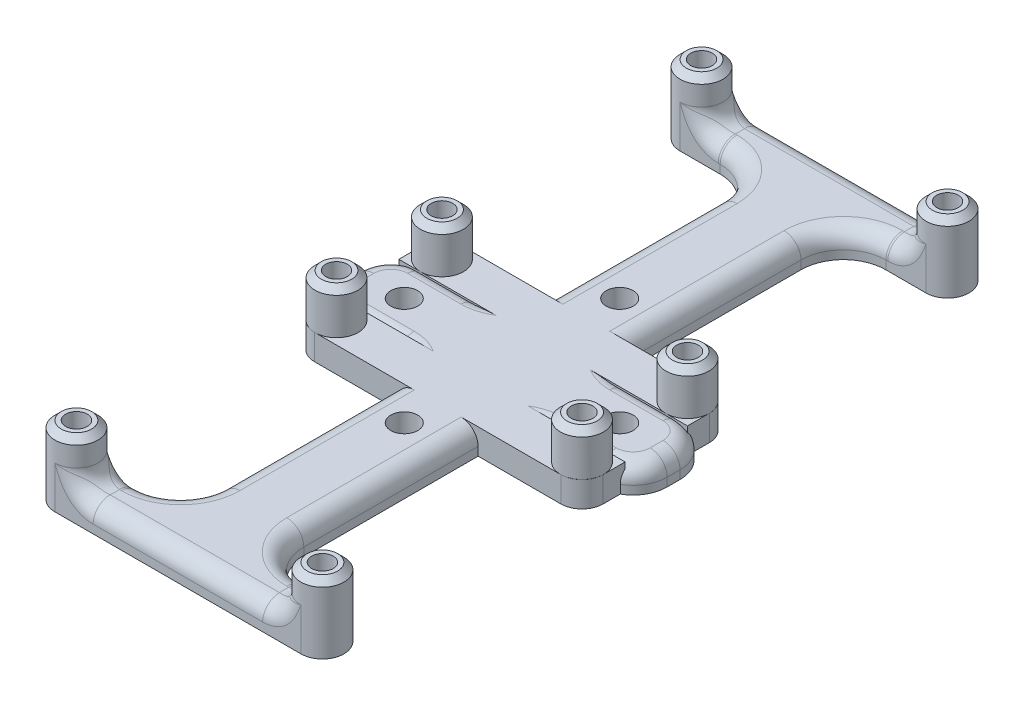
SolidWorks part; units mm, degrees
ref_plane "Front Plane" through (0, 0, 0) normal (0, 0, 1) x (1, 0, 0)
ref_plane "Top Plane" through (0, 0, 0) normal (0, 1, 0) x (1, 0, 0)
ref_plane "Right Plane" through (0, 0, 0) normal (1, 0, 0) x (0, 0, -1)
sketch "Sketch1" plane through (0, 0, 0) normal (0, 1, 0) x (1, 0, 0)
  line L1 (-4.7625, -34.305) -> (4.7625, -34.305)
  line L2 (-4.7625, -34.305) -> (-4.7625, 34.305)
  line L3 (-4.7625, 34.305) -> (4.7625, 34.305)
  line L4 (4.7625, -34.305) -> (4.7625, 34.305)
  line L5 (-4.7625, -34.305) -> (4.7625, 34.305) construction
  line L6 (-4.7625, 34.305) -> (4.7625, -34.305) construction
  line L7 (-14.5, 39.385) -> (14.5, 39.385)
  line L9 (-14.5, 34.305) -> (14.5, 34.305)
  line L11 (-14.5, 39.385) -> (14.5, 34.305) construction
  line L12 (-14.5, 34.305) -> (14.5, 39.385) construction
  line L13 (-14.5, -39.385) -> (14.5, -39.385)
  line L15 (-14.5, -34.305) -> (14.5, -34.305)
  line L17 (-14.5, -39.385) -> (14.5, -34.305) construction
  line L18 (-14.5, -34.305) -> (14.5, -39.385) construction
  arc A2 (-14.5, 34.305) -> (-14.5, 39.385) centre (-14.5, 36.845) cw
  arc A3 (14.5, 34.305) -> (14.5, 39.385) centre (14.5, 36.845) ccw
  arc A4 (-14.5, -39.385) -> (-14.5, -34.305) centre (-14.5, -36.845) cw
  arc A5 (14.5, -39.385) -> (14.5, -34.305) centre (14.5, -36.845) ccw
  point P0 (0, 0)
  point P6 (0, 36.845)
  point P11 (0, -36.845)
  dimension "D4" = 29
  dimension "D1" = 9.525
  dimension "D2" = 5.08
  dimension "D3" = 5.08
  dimension "D5" = 73.69
extrude "Boss-Extrude1" add sketch "Sketch1" along normal blind 3 contours L13 A5 L15 L1 A4 | L1 L4 L3 L2 | L9 A3 L7 A2 L3 region at (0, 0, 0) region at (0, 0, 36.845) region at (0, 0, -36.845)
sketch "Sketch2" plane through (0, 3, 0) normal (0, 1, 0) x (1, 0, 0)
  line L0 (0, 12.7) -> (0, -12.7) construction
  circle A0 centre (0, 12.7) radius 1.5875
  circle A1 centre (0, -12.7) radius 1.5875
  dimension "D2" = 3.175
  dimension "D3" = 3.175
  dimension "D1" = 25.4
extrude "Cut-Extrude1" cut sketch "Sketch2" against normal through all
sketch "Sketch3" plane through (0, 3, 0) normal (0, 1, 0) x (1, 0, 0)
  circle A0 centre (-14.5, 36.845) radius 2.54
  circle A1 centre (14.5, 36.845) radius 2.54
  circle A2 centre (14.5, -36.845) radius 2.54
  circle A3 centre (-14.5, -36.845) radius 2.54
  arc A4 (-14.5, 39.385) -> (-14.5, 34.305) centre (-14.5, 36.845) ccw construction
  arc A5 (14.5, 34.305) -> (14.5, 39.385) centre (14.5, 36.845) ccw construction
  arc A6 (-14.5, -34.305) -> (-14.5, -39.385) centre (-14.5, -36.845) ccw construction
  arc A7 (14.5, -39.385) -> (14.5, -34.305) centre (14.5, -36.845) ccw construction
extrude "Boss-Extrude2" add sketch "Sketch3" along normal blind 5.08
sketch "Sketch4" plane through (0, 8.08, 0) normal (0, 1, 0) x (1, 0, 0)
  circle A0 centre (-14.5, 36.845) radius 1.27
  circle A1 centre (14.5, 36.845) radius 1.27
  circle A2 centre (14.5, -36.845) radius 1.27
  circle A3 centre (-14.5, -36.845) radius 1.27
  dimension "D1" = 2.54
  dimension "D2" = 2.54
  dimension "D3" = 2.54
  dimension "D4" = 2.54
extrude "Cut-Extrude2" cut sketch "Sketch4" against normal blind 3.2004
sketch "Sketch5" plane through (0, 4.8796, 0) normal (0, 1, 0) x (1, 0, 0)
  circle A0 centre (-14.5, 36.845) radius 0.875
  circle A1 centre (14.5, 36.845) radius 0.875
  circle A2 centre (14.5, -36.845) radius 0.875
  circle A3 centre (-14.5, -36.845) radius 0.875
  dimension "D1" = 1.75
  dimension "D2" = 1.75
  dimension "D3" = 1.75
  dimension "D4" = 1.75
extrude "Cut-Extrude3" cut sketch "Sketch5" against normal through all
chamfer "Chamfer1" distance 0.75 angle 45 4 edges at (-14.5, 8.08, -34.305) (14.5, 8.08, -34.305) (14.5, 8.08, 39.385) (-14.5, 8.08, 39.385)
fillet "Fillet1" radius 5 4 edges at (-4.7625, 1.5, -34.305) (4.7625, 1.5, -34.305) (-4.7625, 1.5, 34.305) (4.7625, 1.5, 34.305)
fillet "Fillet2" radius 2 4 edges at (-11.96, 3, 36.845) (11.96, 3, 36.845) (11.96, 3, -36.845) (-11.96, 3, -36.845)
sketch "Sketch6" plane through (0, 3, 0) normal (0, 1, 0) x (1, 0, 0)
  line L1 (-19.05, -4.7625) -> (19.05, -4.7625)
  line L2 (-19.05, -4.7625) -> (-19.05, 4.7625)
  line L3 (-19.05, 4.7625) -> (19.05, 4.7625)
  line L4 (19.05, -4.7625) -> (19.05, 4.7625)
  line L5 (-19.05, -4.7625) -> (19.05, 4.7625) construction
  line L6 (-19.05, 4.7625) -> (19.05, -4.7625) construction
  point P0 (0, 0)
  dimension "D1" = 9.525
  dimension "D2" = 38.1
extrude "Boss-Extrude3" add sketch "Sketch6" against normal up to surface (3 mm away) up to face at (-14.5, 0, 37.72)
fillet "Fillet3" radius 4 8 edges at (-4.7625, 1.5, -4.7625) (-19.05, 1.5, -4.7625) (-19.05, 1.5, 4.7625) (-4.7625, 1.5, 4.7625) (4.7625, 1.5, 4.7625) (4.7625, 1.5, -4.7625) (19.05, 1.5, 4.7625) (19.05, 1.5, -4.7625)
sketch "Sketch7" plane through (0, 3, 0) normal (0, 1, 0) x (1, 0, 0)
  line L0 (-12.7, 0) -> (12.7, 0) construction
  circle A0 centre (-12.7, 0) radius 1.5875
  circle A1 centre (12.7, 0) radius 1.5875
  dimension "D2" = 3.175
  dimension "D3" = 3.175
  dimension "D1" = 25.4
extrude "Cut-Extrude4" cut sketch "Sketch7" against normal through all
fillet "Fillet4" radius 2 30 edges at (11.737, 3.1613, 34.305) (10.2498, 3, 34.305) (6.227, 3, 32.8405) (4.7625, 3, 19.0337) (11.737, 3.1613, -34.305) (10.2498, 3, -34.305) (6.227, 3, -32.8405) (4.7625, 3, -19.0337) (5.9341, 3, -5.9341) (11.9062, 3, -4.7625) (17.8784, 3, -3.5909) (19.05, 3, 0) (17.8784, 3, 3.5909) (11.9062, 3, 4.7625) (-11.737, 3.1613, 34.305) (-10.2498, 3, 34.305) (-6.227, 3, 32.8405) (-11.737, 3.1613, -34.305) (-10.2498, 3, -34.305) (-6.227, 3, -32.8405) (-4.7625, 3, -19.0337) (-5.9341, 3, -5.9341) (-11.9063, 3, -4.7625) (-17.8784, 3, -3.5909) (-19.05, 3, 0) (-17.8784, 3, 3.5909) (-11.9063, 3, 4.7625) (-5.9341, 3, 5.9341) (5.9341, 3, 5.9341) (-4.7625, 3, 19.0337)
fillet "Fillet5" radius 2 6 edges at (-11.737, 3.1613, -39.385) (11.737, 3.1613, -39.385) (-11.737, 3.1613, 39.385) (11.737, 3.1613, 39.385) (0, 3, -39.385) (0, 3, 39.385)
sketch "Sketch8" plane through (0, 0, 0) normal (0, 1, 0) x (1, 0, 0)
  line L0 (0, 0) -> (0, -39.385) construction
  line L1 (9.9922, -39.385) -> (-9.9922, -39.385) construction
  line L2 (9.9922, -34.305) -> (9.9922, -39.385) construction
  line L3 (-17.0119, -8.7567) -> (17.0119, -8.7567)
  line L4 (-17.0119, -8.7567) -> (-17.0119, -3.6767)
  line L5 (-17.0119, -3.6767) -> (17.0119, -3.6767)
  line L6 (17.0119, -8.7567) -> (17.0119, -3.6767)
  line L7 (-17.0119, -8.7567) -> (17.0119, -3.6767) construction
  line L8 (-17.0119, -3.6767) -> (17.0119, -8.7567) construction
  circle A0 centre (-14.5, -36.845) radius 2.54 construction
  circle A1 centre (14.5, -36.845) radius 2.54 construction
  point P5 (0, -6.2167)
  point P14 (-14.1714, -39.3637)
  point P15 (17.0119, -36.4681)
  point P18 (0, 0)
  point P21 (0, 0)
  point P22 (0, 0)
  point P23 (0, 0)
  dimension "D1" = 33.147
extrude "Boss-Extrude4" add sketch "Sketch8" along normal blind 3
mirror "Mirror1" about plane through (0, 0, 0) normal (0, 0, 1) of "Boss-Extrude4"
sketch "Sketch9" plane through (0, 3, 0) normal (0, 1, 0) x (1, 0, 0)
  line L0 (-17.0119, 6.2167) -> (17.0119, 6.2167) construction
  line L1 (-17.0119, 3.6767) -> (-17.0119, 8.7567) construction
  line L2 (17.0119, 8.7567) -> (17.0119, 3.6767) construction
  line L3 (-17.0119, -6.2167) -> (17.0119, -6.2167) construction
  line L4 (-17.0119, -3.6767) -> (-17.0119, -8.7567) construction
  line L5 (17.0119, -8.7567) -> (17.0119, -3.6767) construction
  line L6 (2.7625, -8.7567) -> (17.0119, -8.7567) construction
  line L7 (-17.0119, -8.7567) -> (-2.7625, -8.7567) construction
  line L8 (-15.05, 3.6767) -> (-8.7625, 3.6767) construction
  line L9 (2.7625, 8.7567) -> (17.0119, 8.7567) construction
  circle A0 centre (-14.4719, -6.2167) radius 2.54
  circle A1 centre (-14.4719, 6.2167) radius 2.54
  circle A2 centre (14.4719, 6.2167) radius 2.54
  circle A3 centre (14.4719, -6.2167) radius 2.54
extrude "Boss-Extrude5" add sketch "Sketch9" along normal up to surface (5.08 mm away) up to face at (-14.5, 8.08, 38.635)
sketch "Sketch11" plane through (0, 8.08, 0) normal (0, 1, 0) x (1, 0, 0)
  circle A0 centre (14.4719, -6.2167) radius 1.27
  circle A1 centre (14.5, -36.845) radius 1.27 construction
extrude "Cut-Extrude5" cut sketch "Sketch11" against normal up to surface (3.2004 mm away) up to face at (14.5, 4.8796, 37.72)
sketch "Sketch12" plane through (0, 4.8796, 0) normal (0, 1, 0) x (1, 0, 0)
  circle A0 centre (14.4719, -6.2167) radius 0.875
  circle A1 centre (14.5, -36.845) radius 0.875 construction
extrude "Cut-Extrude6" cut sketch "Sketch12" against normal through all
mirror "Mirror2" about plane through (0, 0, 0) normal (1, 0, 0) of "Cut-Extrude5", "Cut-Extrude6" second plane through (0, 0, 0) second plane normal (0, 0, 1)
chamfer "Chamfer2" distance 0.75 angle 45 4 edges at (14.4719, 8.08, 8.7567) (14.4719, 8.08, -3.6767) (-14.4719, 8.08, -3.6767) (-14.4719, 8.08, 8.7567)
fillet "Fillet6" radius 2.5 4 edges at (-17.0119, 1.5, -8.7567) (17.0119, 1.5, -8.7567) (17.0119, 1.5, 8.7567) (-17.0119, 1.5, 8.7567)
